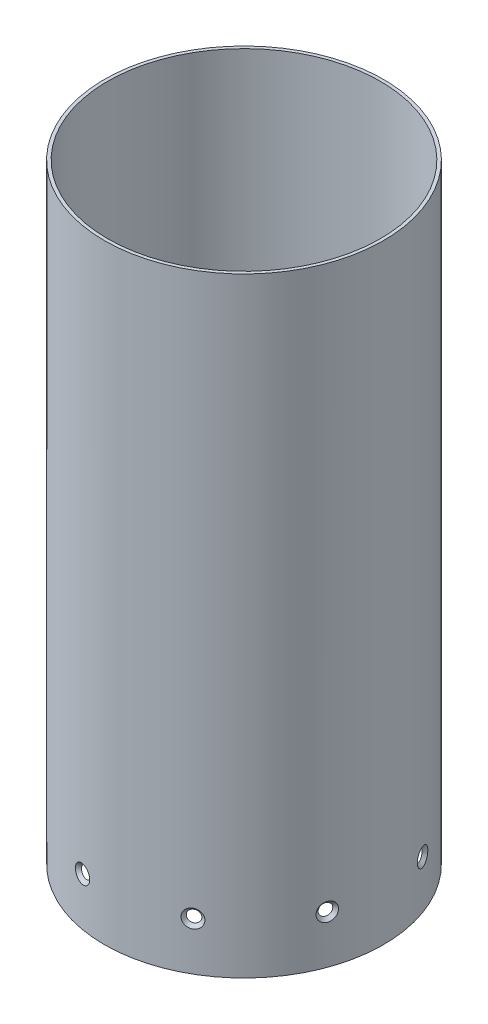
SolidWorks part; units mm, degrees
material "E-Glass Fiber"
ref_plane "Front Plane" through (0, 0, 0) normal (0, 0, 1) x (1, 0, 0)
ref_plane "Top Plane" through (0, 0, 0) normal (0, 1, 0) x (1, 0, 0)
ref_plane "Right Plane" through (0, 0, 0) normal (1, 0, 0) x (0, 0, -1)
sketch "Sketch1" plane through (0, 0, 0) normal (0, 1, 0) x (1, 0, 0)
  circle A0 centre (0, 0) radius 87
  circle A1 centre (0, 0) radius 85
extrude "Boss-Extrude1" add sketch "Sketch1" along normal blind 380
ref_plane "Plane2" through (0, 30, 0) normal (0, -1, 0) x (-1, 0, 0)
ref_plane "Plane1" through (-87, 0, 0) normal (-1, 0, 0) x (0, 0, 1)
sketch "Sketch2" plane through (-87, 0, 0) normal (-1, 0, 0) x (0, 0, 1)
  line L0 (-87, 0) -> (87, 0) construction
  circle A0 centre (0, 30) radius 2.75
  dimension "D1" = 30
extrude "Cut-Extrude1" cut sketch "Sketch2" against normal up to next
sketch "Sketch4" plane through (0, 30, 0) normal (0, -1, 0) x (1, 0, 0)
  line L1 (-93.9937, 0) -> (-74.5658, 0) construction
  line L6 (-86.3554, 0) -> (-86.3554, -5) construction
  line L7 (-86.3554, -5) -> (-81.3554, 0)
  line L8 (-86.3554, 0) -> (-81.3554, 0)
  line L9 (-86.3554, -5) -> (-87.969, -6.6136)
  line L10 (-87.969, -6.6136) -> (-87.969, 0)
  line L11 (-87.969, 0) -> (-86.3554, 0)
  circle A1 centre (0, 0) radius 86.5 construction
revolve "Cut-Revolve1" cut sketch "Sketch4" angle 360 about L1
pattern_circular "CirPattern1" count 9 over 360 about axis through (0, 0, 0) along (0, 1, 0) of "Cut-Revolve1"
